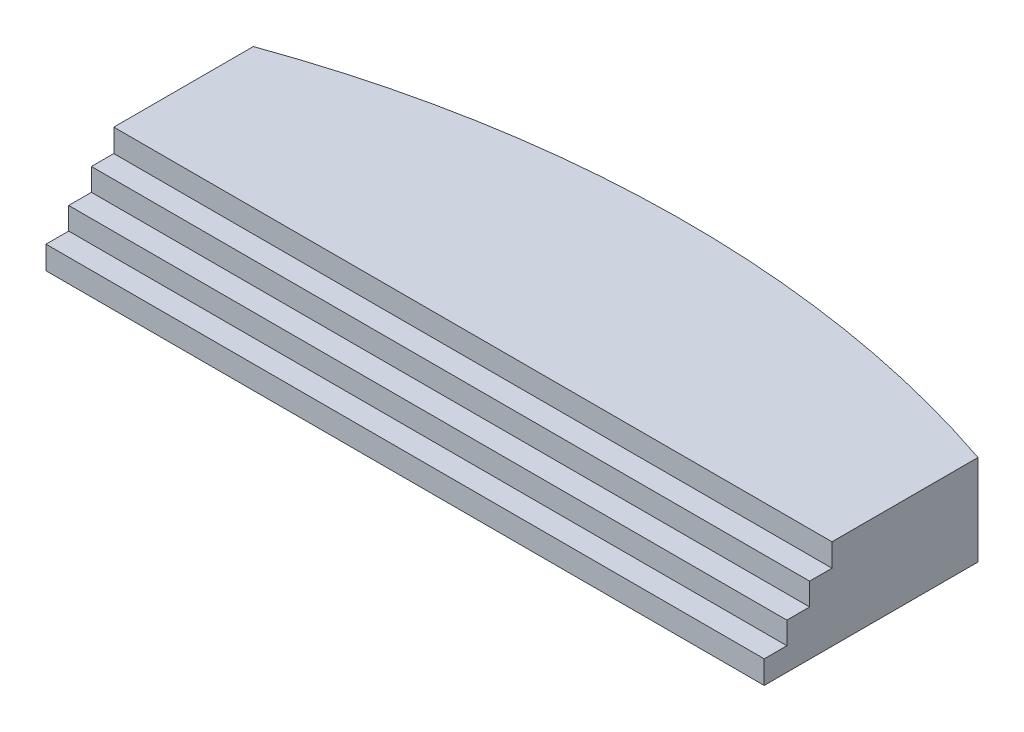
SolidWorks part; units mm, degrees
ref_plane "Front Plane" through (0, 0, 0) normal (0, 0, 1) x (1, 0, 0)
ref_plane "Top Plane" through (0, 0, 0) normal (0, 1, 0) x (1, 0, 0)
ref_plane "Right Plane" through (0, 0, 0) normal (1, 0, 0) x (0, 0, -1)
sketch "Sketch1" plane through (0, 0, 0) normal (0, 1, 0) x (1, 0, 0)
  line L0 (0, 12000) -> (0, 6000) construction
  line L1 (-4067.1162, 9000) -> (3864.1234, 9000)
  line L3 (-4067.1162, 9000) -> (-4067.1162, 11289.7549)
  line L4 (3864.1234, 9000) -> (3864.1234, 11360.8341)
  arc A1 (0, 12000) -> (-4067.1162, 11289.7549) centre (0, 0) ccw
  arc A2 (0, 12000) -> (3864.1234, 11360.8341) centre (0, 0) cw
extrude "Boss-Extrude1" add sketch "Sketch1" along normal blind 1000 contours A2 L4 L1 L3 A1
sketch "Sketch2" plane through (3864.1234, 0, 0) normal (1, 0, 0) x (0, 0, -1)
  line L1 (9000, 1000) -> (9000, 0) construction
  line L2 (9000, 254.9104) -> (9250.2457, 254.9104)
  line L3 (9250.2457, 254.9104) -> (9250.2457, 500)
  line L4 (9250.2457, 500) -> (9501.4119, 500)
  line L5 (9501.4119, 500) -> (9501.4119, 747.1151)
  line L6 (9501.4119, 747.1151) -> (9748.527, 747.1151)
  line L7 (9748.527, 747.1151) -> (9748.527, 1000)
  line L8 (9000, 1000) -> (11360.8341, 1000) construction
  line L9 (9748.527, 1000) -> (9000, 1000)
  line L10 (9000, 1000) -> (9000, 254.9104)
extrude "Cut-Extrude1" cut sketch "Sketch2" against normal blind 24000
